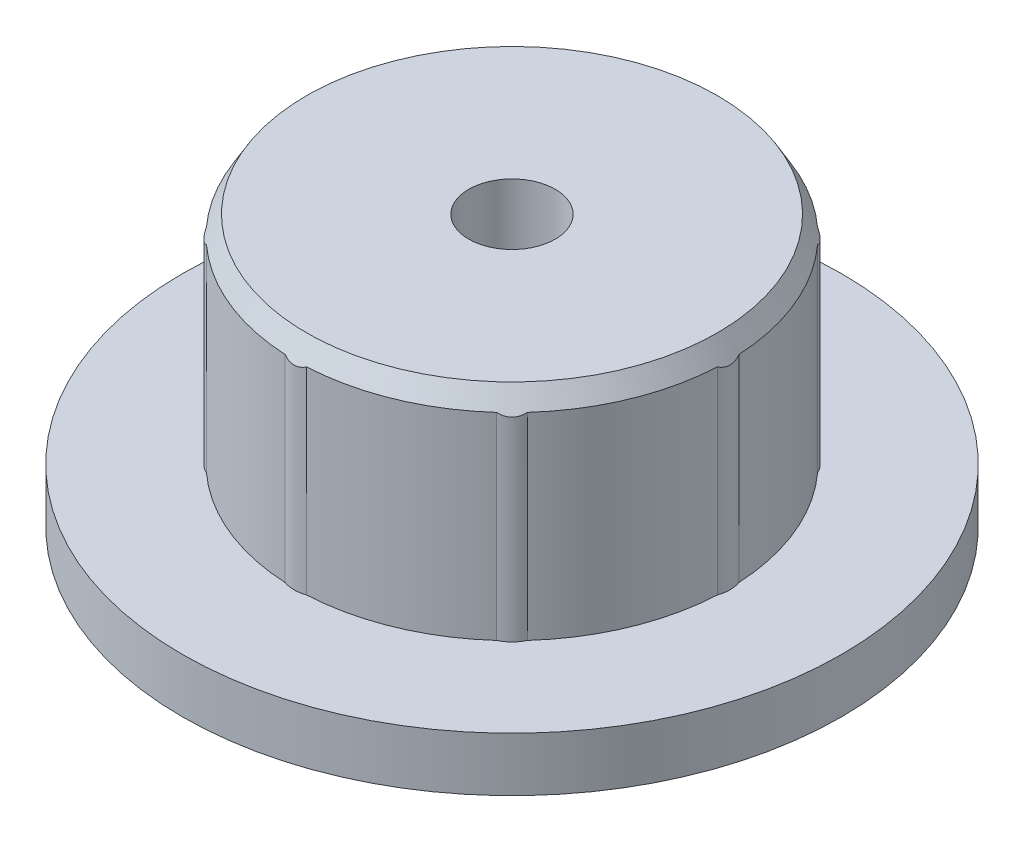
SolidWorks part; units mm, degrees
material "ABS"
ref_plane "Front Plane" through (0, 0, 0) normal (0, 0, 1) x (1, 0, 0)
ref_plane "Top Plane" through (0, 0, 0) normal (0, 1, 0) x (1, 0, 0)
ref_plane "Right Plane" through (0, 0, 0) normal (1, 0, 0) x (0, 0, -1)
sketch "Sketch1" plane through (0, 0, 0) normal (0, 1, 0) x (1, 0, 0)
  line L0 (0, 0) -> (0, 17.2056) construction
  line L1 (0, 0) -> (12.1662, 12.1662) construction
  arc A0 (-1, 19.975) -> (-13.4173, 14.8316) centre (0, 0) ccw
  arc A1 (-1, 19.975) -> (1, 19.975) centre (0, 17.2056) cw
  arc A2 (13.4173, 14.8316) -> (14.8316, 13.4173) centre (12.1662, 12.1662) cw
  arc A3 (19.975, 1) -> (19.975, -1) centre (17.2056, 0) cw
  arc A4 (14.8316, -13.4173) -> (13.4173, -14.8316) centre (12.1662, -12.1662) cw
  arc A5 (1, -19.975) -> (-1, -19.975) centre (0, -17.2056) cw
  arc A6 (-13.4173, -14.8316) -> (-14.8316, -13.4173) centre (-12.1662, -12.1662) cw
  arc A7 (-19.975, -1) -> (-19.975, 1) centre (-17.2056, 0) cw
  arc A8 (-14.8316, 13.4173) -> (-13.4173, 14.8316) centre (-12.1662, 12.1662) cw
  arc A9 (13.4173, 14.8316) -> (1, 19.975) centre (0, 0) ccw
  arc A10 (19.975, 1) -> (14.8316, 13.4173) centre (0, 0) ccw
  arc A11 (14.8316, -13.4173) -> (19.975, -1) centre (0, 0) ccw
  arc A12 (1, -19.975) -> (13.4173, -14.8316) centre (0, 0) ccw
  arc A13 (-13.4173, -14.8316) -> (-1, -19.975) centre (0, 0) ccw
  arc A14 (-19.975, -1) -> (-14.8316, -13.4173) centre (0, 0) ccw
  arc A15 (-14.8316, 13.4173) -> (-19.975, 1) centre (0, 0) ccw
  dimension "D1" = 40
  dimension "D2" = 2
  dimension "D3" = 20.15
  dimension "D5" = 45
  dimension "D4" = 8
extrude "Boss-Extrude1" add sketch "Sketch1" along normal blind 20
sketch "Sketch2" plane through (0, 0, 0) normal (0, 0, 1) x (1, 0, 0)
  line L0 (-18.5623, 20.75) -> (-20.725, 17.0041)
  line L1 (-20.725, 17.0041) -> (-20.725, 20.75)
  line L2 (-20.725, 20.75) -> (-18.5623, 20.75)
  line L3 (-14.8316, 20) -> (-19.975, 20) construction
  line L4 (-19.975, 20) -> (-19.975, 0) construction
  line L5 (0, 0) -> (0, 50000) construction
  dimension "D1" = 30
  dimension "D2" = 0.75
  dimension "D3" = 0.75
  dimension "D4" = 1
revolve "Cut-Revolve1" cut sketch "Sketch2" angle 360 about L5
sketch "Sketch3" plane through (0, 0, 0) normal (0, -1, 0) x (1, 0, 0)
  circle A0 centre (0, 0) radius 30.48
  dimension "D1" = 60.96
extrude "Boss-Extrude2" add sketch "Sketch3" along normal blind 5
sketch "Sketch11" plane through (0, 20, 0) normal (0, 1, 0) x (1, 0, 0)
  circle A0 centre (0, 0) radius 4
  dimension "D1" = 8
extrude "Cut-Extrude2" cut sketch "Sketch11" against normal through all
equation "\"D3@Sketch1\"=40.3/2"
equation "\"D1@Sketch3\"=1.9in+(1/2)*1in"
